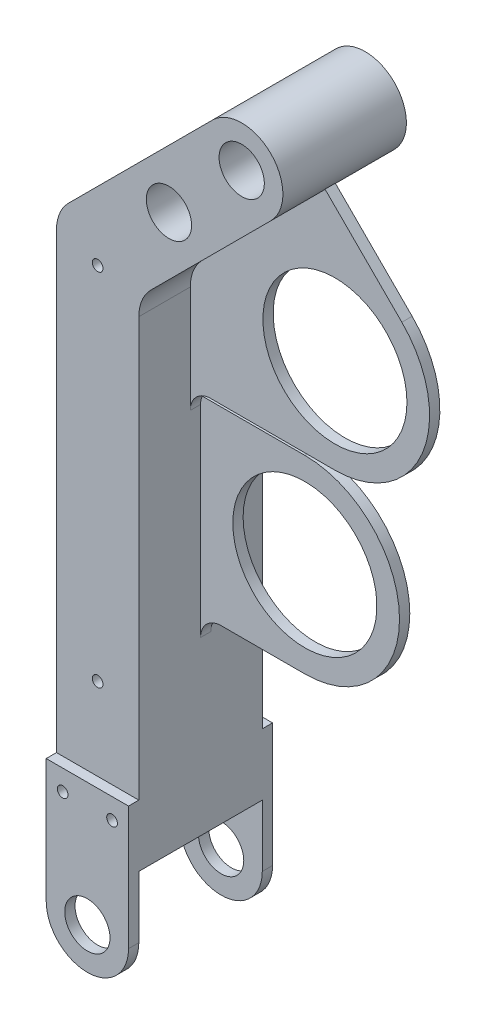
SolidWorks part; units mm, degrees
material "Hexcel AS4C (3000 丝)"
ref_plane "前视基准面" through (0, 0, 0) normal (0, 0, 1) x (1, 0, 0)
ref_plane "上视基准面" through (0, 0, 0) normal (0, 1, 0) x (1, 0, 0)
ref_plane "右视基准面" through (0, 0, 0) normal (1, 0, 0) x (0, 0, -1)
other "Configuration Table"
sketch "草图1" plane through (0, 0, 0) normal (0, 0, 1) x (1, 0, 0)
  circle A0 centre (0, 0) radius 20
  circle A1 centre (0, 0) radius 11
  dimension "D1" = 40
  dimension "D2" = 22
extrude "凸台-拉伸1" add sketch "草图1" along normal blind 60 contours A1 | A0 region at (0, 0, 0)
ref_plane "基准面1" through (0, 0, 30) normal (0, 0, 1) x (1, 0, 0)
sketch "草图2" plane through (0, 0, 30) normal (0, 0, 1) x (1, 0, 0)
  line L0 (0, 0) -> (-70, -70) construction
  line L1 (-70, -70) -> (-70, -320) construction
  line L2 (0, -57.3148) -> (0, 49.9409) construction
  line L3 (-56.8582, 0) -> (46.4003, 0) construction
  line L4 (-14.1421, 14.1421) -> (-90, -61.7157)
  line L5 (14.1421, -14.1421) -> (-50, -78.2843)
  line L6 (-90, -61.7157) -> (-90, -320)
  line L7 (-50, -78.2843) -> (-50, -320)
  line L8 (-90, -320) -> (-50, -320)
  circle A2 centre (0, 0) radius 20 construction
  arc A3 (-14.1421, 14.1421) -> (14.1421, -14.1421) centre (0, 0) ccw
  dimension "D1" = 45
  dimension "D2" = 250
  dimension "D3" = 70
  dimension "D4" = 40
  dimension "D5" = 40
extrude "凸台-拉伸2" add sketch "草图2" along normal mid plane 60 contours L7 L8 L6 L4 A3 L5
sketch "草图4" plane through (0, 0, 60) normal (0, 0, 1) x (1, 0, 0)
  line L0 (-90, -61.7157) -> (-90, -320) construction
  line L1 (-90, -290) -> (-50, -290)
  line L2 (-90, -290) -> (-90, -350)
  line L4 (-50, -290) -> (-50, -350)
  line L5 (-50, -78.2843) -> (-50, -320) construction
  line L6 (-90, -320) -> (-50, -320) construction
  arc A0 (-90, -350) -> (-50, -350) centre (-70, -350) ccw
  circle A1 centre (-70, -350) radius 11
  dimension "D3" = 22
  dimension "D1" = 30
  dimension "D2" = 30
extrude "凸台-拉伸3" add sketch "草图4" along normal blind 5
mirror "镜向1" about plane through (0, 0, 30) normal (0, 0, 1) of "凸台-拉伸3"
sketch "草图5" plane through (0, 0, 0) normal (0, 1, 0) x (1, 0, 0)
  line L0 (0, 0) -> (0, -78.0582) construction
ref_plane "基准面2" through (-70, 0, 0) normal (-1, 0, 0) x (0, 0, 1)
sketch "草图7" plane through (-70, 0, 0) normal (-1, 0, 0) x (0, 0, 1)
  line L0 (-34.1239, -350) -> (109.535, -350) construction
sketch "草图8" plane through (0, 0, 60) normal (0, 0, 1) x (1, 0, 0)
  line L0 (0, 0) -> (-70, -70) construction
  circle A0 centre (-35.3553, -35.3553) radius 11
  dimension "D1" = 22
  dimension "D2" = 50
extrude "切除-拉伸1" cut sketch "草图8" against normal blind 100
fillet "圆角4" radius 20 2 edges at (-90, -61.7157, 30) (-50, -78.2843, 30)
fillet "圆角1" [suppressed] radius 50
fillet "圆角2" [suppressed] radius 3
sketch "草图9" plane through (0, 0, 65) normal (0, 0, 1) x (1, 0, 0)
  circle A0 centre (-70, -350) radius 13
  dimension "D1" = 26
extrude "切除-拉伸2" [suppressed] cut sketch "草图9" against normal blind 0.75
sketch "草图10" plane through (0, 0, -5) normal (0, 0, -1) x (-1, 0, 0)
  circle A0 centre (70, -350) radius 13
  dimension "D1" = 26
extrude "切除-拉伸3" [suppressed] cut sketch "草图10" against normal blind 0.75 contours A0
sketch "草图11" plane through (-90, 0, 0) normal (-1, 0, 0) x (0, 0, 1)
  circle A0 centre (48.5, -118.9949) radius 2.75
  circle A1 centre (48.5, -183.9949) radius 2.75
  circle A2 centre (48.5, -248.9949) radius 2.75
  circle A3 centre (11.5, -248.9949) radius 2.75
  circle A4 centre (11.5, -183.9949) radius 2.75
  circle A5 centre (11.5, -118.9949) radius 2.75
  dimension "D1" = 5.5
extrude "切除-拉伸4" [suppressed] cut sketch "草图11" against normal through all contours A1 | A2 | A0 | A3 | A4 | A5
sketch "草图12" [suppressed] plane through (-90, 0, 0) normal (-1, 0, 0) x (0, 0, 1)
  line L0 (30, -62.0134) -> (30, -339.6946) construction
  line L1 (10, -128.9949) -> (50, -128.9949)
  line L2 (10, -128.9949) -> (10, -173.9949)
  line L3 (10, -173.9949) -> (50, -173.9949)
  line L4 (50, -128.9949) -> (50, -173.9949)
  line L5 (10, -193.9949) -> (50, -193.9949)
  line L6 (10, -193.9949) -> (10, -238.9949)
  line L7 (10, -238.9949) -> (50, -238.9949)
  line L8 (50, -193.9949) -> (50, -238.9949)
  line L9 (10, -258.9949) -> (50, -258.9949)
  line L10 (10, -258.9949) -> (10, -290)
  line L11 (10, -290) -> (50, -290)
  line L12 (50, -258.9949) -> (50, -290)
  line L13 (19.5, -173.9949) -> (40.5, -173.9949)
  line L14 (19.5, -173.9949) -> (19.5, -193.9949)
  line L15 (19.5, -193.9949) -> (40.5, -193.9949)
  line L16 (40.5, -173.9949) -> (40.5, -193.9949)
  line L17 (19.5, -238.9949) -> (40.5, -238.9949)
  line L18 (19.5, -238.9949) -> (19.5, -258.9949)
  line L19 (19.5, -258.9949) -> (40.5, -258.9949)
  line L20 (40.5, -238.9949) -> (40.5, -258.9949)
  line L21 (60, -82.4264) -> (60, -290) construction
  line L22 (0, -290) -> (0, -82.4264) construction
  line L23 (57, -320) -> (3, -320) construction
  circle A0 centre (48.5, -118.9949) radius 2.75 construction
  circle A1 centre (48.5, -183.9949) radius 2.75 construction
  circle A2 centre (48.5, -248.9949) radius 2.75 construction
  dimension "D1" = 10
  dimension "D2" = 10
  dimension "D3" = 10
  dimension "D4" = 8
  dimension "D5" = 10
  dimension "D6" = 10
  dimension "D7" = 10
  dimension "D8" = 30
extrude "减重" [suppressed] cut sketch "草图12" against normal through all contours L0 L1 L2 L3 | L15 L0 L17 L7 L8 L5 | L0 L5 L6 L7 | L19 L0 L11 L12 L9 | L0 L9 L10 L11 | L1 L0 L13 L3 L4
fillet "圆角3" [suppressed] radius 3
sketch "草图13" plane through (0, 0, 60) normal (0, 0, 1) x (1, 0, 0)
  circle A0 centre (0, 0) radius 13
  circle A1 centre (-35.3553, -35.3553) radius 13
  dimension "D1" = 26
  dimension "D2" = 26
extrude "切除-拉伸6" [suppressed] cut sketch "草图13" against normal blind 1.75
sketch "草图14" plane through (0, 0, 0) normal (0, 0, -1) x (-1, 0, 0)
  circle A0 centre (0, 0) radius 13
  circle A1 centre (35.3553, -35.3553) radius 13
  dimension "D1" = 26
  dimension "D2" = 26
extrude "切除-拉伸7" [suppressed] cut sketch "草图14" against normal blind 1.75
sketch "草图15" [suppressed] plane through (0, 0, 0) normal (0, 0, -1) x (-1, 0, 0)
  line L0 (0, 0) -> (70, -350) construction
  line L1 (56.2719, -67.2005) -> (60.1942, -86.8121) construction
  line L2 (70, -350) -> (204.3541, -323.1292) construction
  circle A0 centre (56.2719, -67.2005) radius 2.75
  circle A1 centre (75.2172, -73.6095) radius 2.75
  circle A2 centre (60.1942, -86.8121) radius 2.75
  dimension "D1" = 5.5
  dimension "D2" = 20
  dimension "D3" = 20
  dimension "D4" = 20
  dimension "D5" = 42
  dimension "D6" = 270
extrude "切除-拉伸8" [suppressed] cut sketch "草图15" against normal through all contours A2 | A0 | A1
ref_plane "小腿主干连杆面" through (0, 0, 0) normal (0.9806, -0.1961, 0) x (0, 0, -1)
ref_plane "小腿主干对称面" through (0, 0, 30) normal (0, 0, -1) x (-1, 0, 0)
sketch "草图16" plane through (0, 0, 60) normal (0, 0, 1) x (1, 0, 0)
  line L0 (0, 0) -> (-70, -350)
  line L1 (-35.3553, -35.3553) -> (0, 0)
sketch "草图17" plane through (0, 0, 60) normal (0, 0, 1) x (1, 0, 0)
  line L0 (0, 0) -> (-70, -350) construction
  line L1 (118.6974, 32.5948) -> (32.9122, -396.3312) construction
  line L2 (92.7764, -97.0102) -> (20.2919, -82.5133)
  line L3 (73.1648, -195.0683) -> (0.6803, -180.5713)
  circle A0 centre (20.2919, -82.5133) radius 46
  circle A1 centre (0.6803, -180.5713) radius 46
  dimension "D3" = 92
  dimension "D4" = 92
  dimension "D1" = 110
  dimension "D2" = 73.92
  dimension "D5" = 180
  dimension "D6" = 280
sketch "草图18" plane through (0, 0, 60) normal (0, 0, 1) x (1, 0, 0)
  line L1 (14.1421, -14.1421) -> (-44.1421, -72.4264) construction
  line L3 (14.1421, -14.1421) -> (-44.1421, -72.4264)
  line L4 (15.4873, -12.6548) -> (52.8188, -49.9864)
  line L5 (-50, -128.5133) -> (20.2919, -128.5133)
  line L10 (-90, -290) -> (-50, -290)
  line L11 (-50, -290) -> (-50, -86.5685)
  line L12 (-44.1421, -72.4264) -> (14.1421, -14.1421)
  line L13 (-14.1421, 14.1421) -> (-84.1421, -55.8579)
  line L14 (-90, -70) -> (-90, -290)
  line L16 (-50, -128.5133) -> (-50, -86.5685)
  line L17 (-44.1421, -72.4264) -> (14.1421, -14.1421)
  circle A0 centre (20.2919, -82.5133) radius 46 construction
  arc A1 (14.1421, -14.1421) -> (-14.1421, 14.1421) centre (0, 0) ccw construction
  arc A2 (14.1421, -14.1421) -> (-14.1421, 14.1421) centre (0, 0) ccw
  arc A3 (14.1421, -14.1421) -> (15.4873, -12.6548) centre (0, 0) ccw
  arc A4 (20.2919, -128.5133) -> (52.8188, -49.9864) centre (20.2919, -82.5133) ccw
  circle A5 centre (20.2919, -82.5133) radius 35
  arc A9 (-84.1421, -55.8579) -> (-90, -70) centre (-70, -70) ccw
  arc A10 (-84.1421, -55.8579) -> (-90, -70) centre (-70, -70) ccw
  arc A11 (-44.1421, -72.4264) -> (-50, -86.5685) centre (-30, -86.5685) ccw
  arc A12 (-44.1421, -72.4264) -> (-50, -86.5685) centre (-30, -86.5685) ccw
  line M14 (-50, -290) -> (-50, -86.5685)
  line M15 (-44.1421, -72.4264) -> (14.1421, -14.1421)
  arc M16 (14.1421, -14.1421) -> (-14.1421, 14.1421) centre (0, 0) ccw
  arc M22 (-50, -86.5685) -> (-44.1421, -72.4264) centre (-30, -86.5685) cw
  dimension "D2" = 70
  dimension "D1" = 0
extrude "凸台-拉伸4" add sketch "草图18" against normal blind 5 from offset 25 contours L5 A4 L4 A5 M16 M15 M22 M14 region at (16.0508, -14.5165, 60) offset against normal yes
sketch "草图19" plane through (0, 0, 0) normal (0, 0, -1) x (-1, 0, 0)
  line L0 (50, -86.5685) -> (50, -290) construction
  line L1 (50, -134.5713) -> (50, -226.5713)
  line L2 (-0.6803, -134.5713) -> (50, -134.5713)
  line L3 (-0.6803, -226.5713) -> (50, -226.5713)
  circle A0 centre (-0.6803, -180.5713) radius 46 construction
  arc A1 (-0.6803, -134.5713) -> (-0.6803, -226.5713) centre (-0.6803, -180.5713) ccw
  circle A2 centre (-0.6803, -180.5713) radius 35
  dimension "D1" = 70
extrude "凸台-拉伸5" add sketch "草图19" against normal blind 5 from offset 25 offset against normal yes
fillet "圆角5" radius 10 2 edges at (-50, -226.5713, 27.5) (-50, -128.5133, 32.5)
sketch "草图21" plane through (0, 0, 65) normal (0, 0, 1) x (1, 0, 0)
  line L0 (-70, -350) -> (-70, -6.9331) construction
  circle A0 centre (-70, -75) radius 2.6
  circle A1 centre (-70, -250) radius 2.6
  circle A2 centre (-58, -300) radius 2.6
  circle A3 centre (-82, -300) radius 2.6
  point P11 (0, 0)
  dimension "D1" = 5.2
  dimension "D2" = 12
  dimension "D3" = 50
  dimension "D4" = 100
  dimension "D5" = 175
extrude "切除-拉伸9" cut sketch "草图21" against normal through all both and the other way through all
